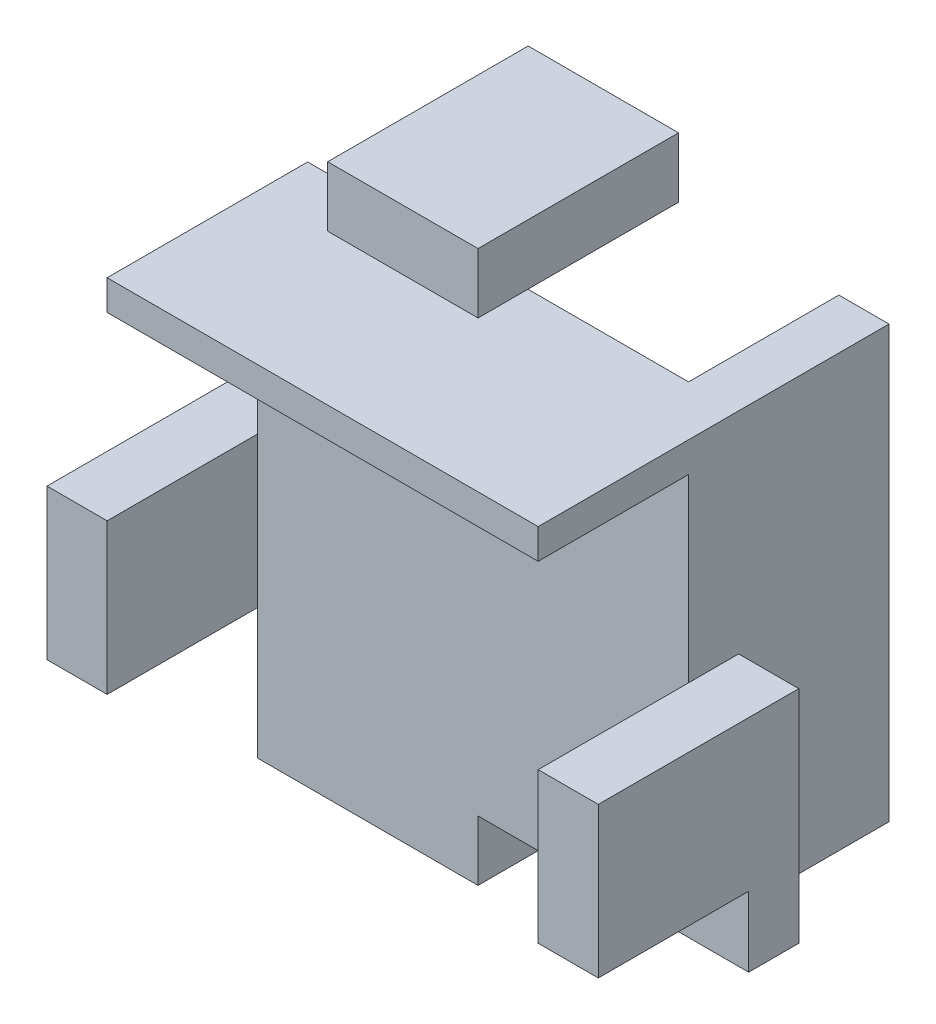
SolidWorks part; units mm, degrees
material "ABS"
ref_plane "前视基准面" through (0, 0, 0) normal (0, 0, 1) x (1, 0, 0)
ref_plane "上视基准面" through (0, 0, 0) normal (0, 1, 0) x (1, 0, 0)
ref_plane "右视基准面" through (0, 0, 0) normal (1, 0, 0) x (0, 0, -1)
sketch "草图1" plane through (0, 0, 0) normal (0, 0, 1) x (1, 0, 0)
  line L0 (-50.797, 9.0326) -> (-50.797, 3.0326)
  line L1 (-77.797, 31.0326) -> (-71.797, 31.0326)
  line L2 (-77.797, 31.0326) -> (-77.797, 9.0326)
  line L3 (-77.797, 9.0326) -> (-50.797, 9.0326)
  line L4 (-22.797, 31.0326) -> (-22.797, 9.0326)
  line L5 (-50.797, 58.0326) -> (-28.797, 58.0326)
  line L6 (-50.797, 58.0326) -> (-50.797, 52.0326)
  line L7 (-50.797, 3.0326) -> (-28.797, 3.0326)
  line L8 (-28.797, 58.0326) -> (-28.797, 31.0326)
  line L9 (-28.797, 9.0326) -> (-28.797, 3.0326)
  line L10 (-28.797, 9.0326) -> (-22.797, 9.0326)
  line L11 (-28.797, 31.0326) -> (-22.797, 31.0326)
  line L12 (-50.797, 49.0326) -> (-50.797, 31.0326)
  line L13 (-50.797, 9.0326) -> (-35.797, 9.0326)
  line L14 (-50.797, 9.0326) -> (-50.797, 3.0326)
  line L15 (-50.797, 3.0326) -> (-35.797, 3.0326)
  line L16 (-35.797, 9.0326) -> (-35.797, 3.0326)
  line L17 (-50.797, 52.0326) -> (-35.797, 52.0326)
  line L18 (-50.797, 52.0326) -> (-50.797, 58.0326)
  line L19 (-50.797, 58.0326) -> (-35.797, 58.0326)
  line L20 (-35.797, 52.0326) -> (-35.797, 58.0326)
  line L21 (-28.797, 31.0326) -> (-22.797, 31.0326)
  line L22 (-28.797, 31.0326) -> (-28.797, 16.0326)
  line L23 (-28.797, 16.0326) -> (-22.797, 16.0326)
  line L24 (-22.797, 31.0326) -> (-22.797, 16.0326)
  line L25 (-77.797, 31.0326) -> (-71.797, 31.0326)
  line L26 (-77.797, 31.0326) -> (-77.797, 16.0326)
  line L27 (-77.797, 16.0326) -> (-71.797, 16.0326)
  line L28 (-71.797, 31.0326) -> (-71.797, 16.0326)
  line L29 (-68.797, 9.0326) -> (-71.797, 9.0326)
  line L30 (-68.797, 9.0326) -> (-68.797, 49.0326)
  line L31 (-68.797, 49.0326) -> (-71.797, 49.0326)
  line L32 (-71.797, 9.0326) -> (-71.797, 49.0326)
  line L33 (-28.797, 49.0326) -> (-71.797, 49.0326)
  line L34 (-28.797, 49.0326) -> (-28.797, 52.0326)
  line L35 (-28.797, 52.0326) -> (-71.797, 52.0326)
  line L36 (-71.797, 49.0326) -> (-71.797, 52.0326)
  line L37 (-68.797, 31.0326) -> (-50.797, 31.0326)
  dimension "D1" = 55
  dimension "D2" = 22
  dimension "D3" = 55
  dimension "D4" = 22
  dimension "D5" = 6
  dimension "D6" = 6
  dimension "D7" = 15
  dimension "D8" = 6
  dimension "D9" = 15
  dimension "D10" = 15
  dimension "D11" = 6
  dimension "D12" = 15
  dimension "D13" = 3
  dimension "D14" = 40
extrude "拉伸-薄壁3" add sketch "草图1" along normal blind 15 thin contours L11 thin type one direction wall 15
extrude "凸台-拉伸3" add sketch "草图1<7>" along normal blind 15 separate body contours L28 L1 L2 L27 region at (-74.797, 23.5326, 0)
sketch "草图1<7>" plane through (0, 0, 0) normal (0, 0, 1) x (1, 0, 0) same geometry as "草图1"
extrude "凸台-拉伸4" add sketch "草图1<8>" along normal blind 15 separate body contours L36 L31 L33 L8 L35 L17 region at (-50.297, 50.5326, 0)
sketch "草图1<8>" plane through (0, 0, 0) normal (0, 0, 1) x (1, 0, 0) same geometry as "草图1"
extrude "凸台-拉伸5" add sketch "草图1<11>" against normal blind 5 contours L37 L30 L3 L13 L16 L7 L9 L10 L4 L23 L22 L8 L33 L12 | L30 L37 L12 L33 | L22 L23 L4 L11 | L28 L1 L2 L27 | L32 L3 L30 L31 L28 | L36 L31 L33 L8 L35 L17 | L17 L20 L5 L6 | L35 L8 L5 L20 | L16 L13 L0 L7 region at (-43.297, 6.0326, 0) region at (-44.9565, 25.1922, 0) region at (-70.297, 29.0326, 0) region at (-59.797, 40.0326, 0) region at (-74.797, 23.5326, 0) region at (-50.297, 50.5326, 0) region at (-25.797, 23.5326, 0) region at (-43.297, 55.0326, 0) region at (-32.297, 55.0326, 0)
sketch "草图1<11>" plane through (0, 0, 0) normal (0, 0, 1) x (1, 0, 0) same geometry as "草图1"
extrude "凸台-拉伸10" add sketch "草图1<13>" against normal blind 20 contours L32 L29 L30 L31
sketch "草图1<13>" plane through (0, 0, 0) normal (0, 0, 1) x (1, 0, 0) same geometry as "草图1"
sketch "草图3" plane through (0, 0, -5) normal (0, 0, -1) x (-1, 0, 0)
  line L0 (50.797, 58.0326) -> (28.797, 58.0326) construction
  line L1 (35.9279, 58.0326) -> (50.797, 58.0326)
  line L2 (35.9279, 58.0326) -> (35.9279, 52.0326)
  line L3 (35.9279, 52.0326) -> (50.797, 52.0326)
  line L4 (50.797, 58.0326) -> (50.797, 52.0326)
  line L5 (50.797, 3.0326) -> (28.797, 3.0326) construction
  line L6 (50.797, 9.0326) -> (35.9279, 9.0326)
  line L7 (50.797, 9.0326) -> (50.797, 3.0326)
  line L8 (50.797, 3.0326) -> (35.9279, 3.0326)
  line L9 (35.9279, 9.0326) -> (35.9279, 3.0326)
extrude "凸台-拉伸15" add sketch "草图3" along normal blind 15
sketch "草图4" plane through (0, 0, -5) normal (0, 0, -1) x (-1, 0, 0)
  line L2 (50.797, 52.0326) -> (28.797, 52.0326)
  line L3 (50.797, 52.0326) -> (50.797, 58.0326)
  line L4 (50.797, 58.0326) -> (28.797, 58.0326)
  line L5 (28.797, 52.0326) -> (28.797, 58.0326)
  line L6 (71.797, 52.0326) -> (64.797, 52.0326)
  line L7 (71.797, 52.0326) -> (71.797, 58.0326)
  line L8 (71.797, 58.0326) -> (64.797, 58.0326)
  line L9 (64.797, 52.0326) -> (64.797, 58.0326)
  dimension "D1" = 6
  dimension "D2" = 7
extrude "切除-拉伸2" cut sketch "草图4" against normal through all
sketch "草图8" plane through (0, 0, -20) normal (0, 0, -1) x (-1, 0, 0)
  line L0 (50.797, 58.0326) -> (35.9279, 58.0326) construction
  line L1 (35.9279, 58.0326) -> (50.797, 58.0326)
  line L2 (35.9279, 58.0326) -> (35.9279, 52.0326)
  line L3 (35.9279, 52.0326) -> (50.797, 52.0326)
  line L4 (50.797, 58.0326) -> (50.797, 52.0326)
  line L5 (35.9279, 58.0326) -> (35.9279, 52.0326) construction
extrude "切除-拉伸3" cut sketch "草图8" against normal through all
sketch "草图10" plane through (0, 0, 0) normal (0, 0, 1) x (1, 0, 0)
  line L0 (-71.797, 49.0326) -> (-71.797, 52.0326) construction
  line L1 (-64.797, 52.0532) -> (-49.797, 52.0532)
  line L2 (-64.797, 52.0532) -> (-64.797, 58.0532)
  line L3 (-64.797, 58.0532) -> (-49.797, 58.0532)
  line L4 (-49.797, 52.0532) -> (-49.797, 58.0532)
  dimension "D1" = 15
  dimension "D2" = 6
  dimension "D3" = 7
extrude "凸台-拉伸16" add sketch "草图10" against normal up to vertex (20 mm away) separate body up to point (-35.9279, 3.0326, -20)
sketch "草图13" plane through (0, 0, 0) normal (0, 0, 1) x (1, 0, 0)
  line L1 (-50.797, 9.0326) -> (-28.797, 9.0326)
  line L2 (-50.797, 9.0326) -> (-50.797, 3.0326)
  line L3 (-50.797, 3.0326) -> (-28.797, 3.0326)
  line L4 (-28.797, 9.0326) -> (-28.797, 3.0326)
extrude "切除-拉伸4" cut sketch "草图13" against normal through all
sketch "草图15" plane through (0, 0, 0) normal (0, 0, 1) x (1, 0, 0)
  line L1 (-71.797, 9.0326) -> (-64.797, 9.0326)
  line L2 (-71.797, 9.0326) -> (-71.797, 3.0326)
  line L3 (-71.797, 3.0326) -> (-64.797, 3.0326)
  line L4 (-64.797, 9.0326) -> (-64.797, 3.0326)
  line L5 (-64.797, 9.0326) -> (-49.797, 9.0326)
  line L6 (-64.797, 9.0326) -> (-64.797, 3.0326)
  line L7 (-64.797, 3.0326) -> (-49.797, 3.0326)
  line L8 (-49.797, 9.0326) -> (-49.797, 3.0326)
  dimension "D1" = 6
  dimension "D2" = 7
  dimension "D3" = 15
extrude "凸台-拉伸17" add sketch "草图15" against normal blind 5 contours L3 L4 L1 L2
sketch "草图16" plane through (0, 0, 0) normal (0, 0, 1) x (1, 0, 0)
  line L0 (-64.797, 9.0326) -> (-22.797, 9.0326) construction
  line L1 (-64.797, 3.0326) -> (-49.797, 3.0326)
  line L2 (-64.797, 3.0326) -> (-64.797, 9.0326)
  line L3 (-64.797, 9.0326) -> (-49.797, 9.0326)
  line L4 (-49.797, 3.0326) -> (-49.797, 9.0326)
  dimension "D1" = 15
extrude "凸台-拉伸18" add sketch "草图16" against normal up to vertex (20 mm away) up to point (-64.797, 52.0532, -20)
sketch "草图17" plane through (0, 0, -5) normal (0, 0, -1) x (-1, 0, 0)
  line L1 (68.797, 49.0326) -> (71.797, 49.0326)
  line L2 (68.797, 49.0326) -> (68.797, 9.0326)
  line L3 (68.797, 9.0326) -> (71.797, 9.0326)
  line L4 (71.797, 49.0326) -> (71.797, 9.0326)
extrude "切除-拉伸5" cut sketch "草图17" along normal through all contours L2 L3 L4 L1
sketch "草图18" plane through (0, 0, -5) normal (0, 0, -1) x (-1, 0, 0)
  line L0 (49.797, 9.0326) -> (22.797, 9.0326) construction
  line L1 (28.797, 52.0326) -> (33.797, 52.0326)
  line L2 (28.797, 52.0326) -> (28.797, 9.0326)
  line L3 (28.797, 9.0326) -> (33.797, 9.0326)
  line L4 (33.797, 52.0326) -> (33.797, 9.0326)
  dimension "D1" = 5
extrude "凸台-拉伸19" add sketch "草图18" along normal up to vertex (15 mm away) up to point (-49.797, 58.0532, -20)
